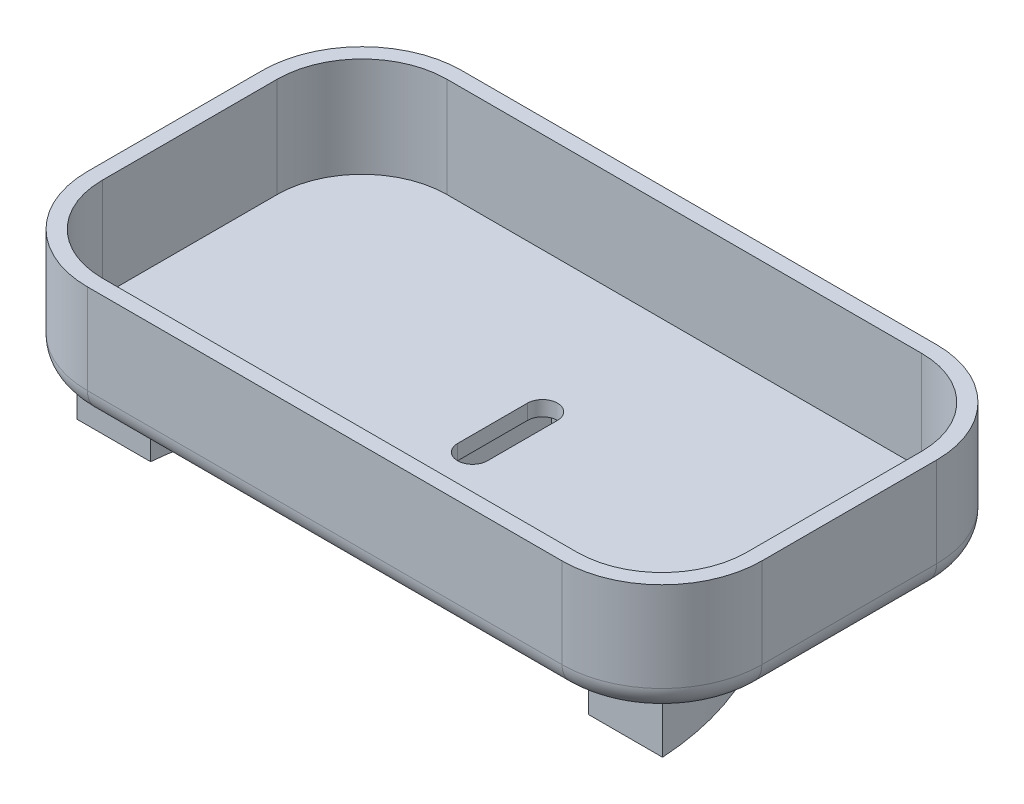
SolidWorks part; units mm, degrees
ref_plane "Front Plane" through (0, 0, 0) normal (0, 0, 1) x (1, 0, 0)
ref_plane "Top Plane" through (0, 0, 0) normal (0, 1, 0) x (1, 0, 0)
ref_plane "Right Plane" through (0, 0, 0) normal (1, 0, 0) x (0, 0, -1)
sketch "Esboço1" plane through (0, 0, 0) normal (0, 1, 0) x (1, 0, 0)
  line L0 (7.7996, 47.1004) -> (7.7996, 20.1004)
  line L1 (7.7996, 20.1004) -> (42.6416, 20.1004)
  line L2 (46.9151, 5.7004) -> (56.2287, 5.7004)
  line L3 (37.717, 41.7004) -> (37.717, 41.7004)
  line L8 (-37.1178, 41.7004) -> (-37.1178, 41.7004)
  line L9 (-55.6295, 5.7004) -> (-46.3158, 5.7004)
  line L10 (-42.0423, 20.1004) -> (-7.2004, 20.1004)
  line L11 (-7.2004, 20.1004) -> (-7.2004, 47.1004)
  line L12 (-7.2004, 47.1004) -> (7.7996, 47.1004)
  line L26 (4.7996, 44.1004) -> (4.7996, 17.1004)
  line L27 (4.7996, 17.1004) -> (40.713, 17.1004)
  line L28 (44.1972, 2.7004) -> (59.4736, 2.7004)
  line L35 (-58.8744, 2.7004) -> (-43.598, 2.7004)
  line L36 (-40.1137, 17.1004) -> (-4.2004, 17.1004)
  line L37 (-4.2004, 17.1004) -> (-4.2004, 44.1004)
  line L38 (-4.2004, 44.1004) -> (4.7996, 44.1004)
  line L39 (-17.7004, 44.7004) -> (-34.5804, 44.7004) construction
  line L40 (-14.7004, 53.9135) -> (-14.7004, 41.7004) construction
  line L41 (-17.7004, 56.15) -> (-17.7004, 44.7004) construction
  line L42 (-14.7004, 41.7004) -> (-37.1178, 41.7004) construction
  line L43 (-34.5804, 44.7004) -> (-34.5804, 47.5955) construction
  line L44 (18.2996, 44.7004) -> (18.2996, 56.15) construction
  line L45 (15.2996, 41.7004) -> (15.2996, 53.9135) construction
  line L46 (37.717, 41.7004) -> (15.2996, 41.7004) construction
  line L47 (35.1796, 44.7004) -> (18.2996, 44.7004) construction
  line L48 (35.1796, 47.5955) -> (35.1796, 44.7004) construction
  arc A0 (46.9151, 5.7004) -> (42.6416, 20.1004) centre (0.2996, -0.2996) ccw
  arc A1 (56.2287, 5.7004) -> (15.2996, 53.9135) centre (0.2996, -0.2996) ccw
  arc A2 (15.2996, 53.9135) -> (-14.7004, 53.9135) centre (0.2996, -0.2996) ccw
  arc A3 (-14.7004, 53.9135) -> (-55.6295, 5.7004) centre (0.2996, -0.2996) ccw
  arc A4 (-42.0423, 20.1004) -> (-46.3158, 5.7004) centre (0.2996, -0.2996) ccw
  arc A5 (-37.1178, 41.7004) -> (-55.6295, 5.7004) centre (0.2996, -0.2996) ccw construction
  arc A6 (-34.5804, 47.5955) -> (-58.8744, 2.7004) centre (0.2996, -0.2996) ccw construction
  arc A7 (56.2287, 5.7004) -> (37.717, 41.7004) centre (0.2996, -0.2996) ccw construction
  arc A8 (59.4736, 2.7004) -> (35.1796, 47.5955) centre (0.2996, -0.2996) ccw construction
  arc A10 (44.1972, 2.7004) -> (40.713, 17.1004) centre (0.2996, -0.2996) ccw
  arc A11 (59.4736, 2.7004) -> (18.2996, 56.15) centre (0.2996, -0.2996) ccw
  arc A12 (18.2996, 56.15) -> (-17.7004, 56.15) centre (0.2996, -0.2996) ccw
  arc A13 (-17.7004, 56.15) -> (-58.8744, 2.7004) centre (0.2996, -0.2996) ccw
  arc A14 (-40.1137, 17.1004) -> (-43.598, 2.7004) centre (0.2996, -0.2996) ccw
  dimension "D1" = 3
extrude "Ressalto-extrusão2" add sketch "Esboço1" along normal blind 10 contours A14 L36 L37 L38 L26 L27 A10 L28 A11 A12 A13 L35 L10 A4 L9 A3 A2 A1 L2 A0 L1 L0 L12 L11 region at (0.2996, 0, -45.4107)
sketch "Esboço3" plane through (0, 10, 0) normal (0, 1, 0) x (1, 0, 0)
  line L0 (-58.8744, 2.7004) -> (59.4736, 2.7004)
  arc A0 (59.4736, 2.7004) -> (-58.8744, 2.7004) centre (0.2996, -0.2996) ccw construction
  arc A1 (59.4736, 2.7004) -> (-58.8744, 2.7004) centre (0.2996, -0.2996) ccw
extrude "Ressalto-extrusão3" add sketch "Esboço3" along normal blind 3
sketch "Esboço4" plane through (0, 10, 0) normal (0, -1, 0) x (1, 0, 0)
  line L0 (0, -24.1004) -> (0, -38.1004) construction
  line L1 (3, -24.1004) -> (3, -38.1004)
  line L2 (-3, -24.1004) -> (-3, -38.1004)
  line L5 (-4.2004, -44.1004) -> (4.7996, -44.1004) construction
  arc A0 (3, -24.1004) -> (-3, -24.1004) centre (0, -24.1004) ccw
  arc A1 (-3, -38.1004) -> (3, -38.1004) centre (0, -38.1004) ccw
  point P3 (0, -31.1004)
  dimension "D1" = 20
  dimension "D3" = 3
  dimension "D2" = 6
extrude "Corte-extrusão1" cut sketch "Esboço4" against normal through all both and the other way through all
sketch "Esboço5" plane through (0, 13, 0) normal (0, 1, 0) x (1, 0, 0)
  line L0 (-58.346, 3.2004) -> (58.9453, 3.2004)
  line L1 (-58.8744, 2.7004) -> (59.4736, 2.7004)
  line L2 (-58.8744, 2.7004) -> (59.4736, 2.7004)
  arc A0 (58.9453, 3.2004) -> (-58.346, 3.2004) centre (0.2996, -0.2996) ccw
  arc A1 (59.4736, 2.7004) -> (-58.8744, 2.7004) centre (0.2996, -0.2996) ccw
  arc A2 (59.4736, 2.7004) -> (-58.8744, 2.7004) centre (0.2996, -0.2996) ccw
  dimension "D1" = 0
  dimension "D2" = 0.5
extrude "Corte-extrusão2" cut sketch "Esboço5" against normal through all
sketch "Esboço7" plane through (0, 13, 0) normal (0, 1, 0) x (1, 0, 0)
  line L0 (-67.2268, -5.7996) -> (-49.8945, -5.7996)
  line L1 (-49.8945, -5.7996) -> (67.826, -5.7996)
  line L4 (-58.346, 3.2004) -> (58.9453, 3.2004)
  line L7 (-58.346, 3.2004) -> (58.9453, 3.2004)
  line L9 (-67.2268, -5.7996) -> (-29.7004, -5.7996) construction
  line L12 (-29.95, 3.6004) -> (29.5415, 3.6004) construction
  line L13 (-37.0345, 12.6004) -> (36.3278, 12.6004) construction
  line L14 (-58.346, 3.2004) -> (-39.045, 3.2004) construction
  arc A1 (67.826, -5.7996) -> (-67.2268, -5.7996) centre (0.2996, -0.2996) ccw
  arc A5 (58.9453, 3.2004) -> (-58.346, 3.2004) centre (0.2996, -0.2996) ccw
  arc A8 (58.9453, 3.2004) -> (-58.346, 3.2004) centre (0.2996, -0.2996) ccw
  arc A12 (-29.95, 3.6004) -> (-29.7004, -5.7996) centre (0.2996, -0.2996) ccw construction
  arc A13 (-49.8945, -5.7996) -> (29.5415, 3.6004) centre (-9.7974, -4.3031) ccw construction
  arc A14 (-37.0345, 12.6004) -> (-39.045, 3.2004) centre (0.2996, -0.2996) ccw construction
  arc A15 (-58.346, 3.2004) -> (36.3278, 12.6004) centre (-9.7974, -4.3031) ccw construction
  dimension "D1" = 0
  dimension "D2" = 9
extrude "Ressalto-extrusão4" add sketch "Esboço7" against normal blind 3
sketch "Esboço13" plane through (0, 13, 0) normal (0, 1, 0) x (1, 0, 0)
  line L0 (-67.2268, -5.7996) -> (-67.2268, 69.2004)
  line L1 (-67.2268, 69.2004) -> (67.826, 69.2004)
  line L2 (67.826, 69.2004) -> (67.826, -5.7996)
  line L3 (67.826, -5.7996) -> (-67.2268, -5.7996)
  line L4 (3, 38.1004) -> (3, 24.1004) construction
  line L5 (-3, 24.1004) -> (-3, 38.1004) construction
  line L6 (3, 38.1004) -> (3, 24.1004)
  line L7 (-3, 24.1004) -> (-3, 38.1004)
  arc A0 (-3, 24.1004) -> (3, 24.1004) centre (0, 24.1004) ccw construction
  arc A1 (3, 38.1004) -> (-3, 38.1004) centre (0, 38.1004) ccw construction
  arc A2 (-3, 24.1004) -> (3, 24.1004) centre (0, 24.1004) ccw
  arc A3 (3, 38.1004) -> (-3, 38.1004) centre (0, 38.1004) ccw
  dimension "D1" = 75
extrude "Ressalto-extrusão10" add sketch "Esboço13" against normal up to surface (3 mm away) up to face at (0.2996, 10, -24.7997)
fillet "Filete1" radius 20 4 edges at (67.826, 11.5, -69.2004) (67.826, 11.5, 5.7996) (-67.2268, 11.5, -69.2004) (-67.2268, 11.5, 5.7996)
sketch "Esboço15" plane through (0, 13, 0) normal (0, 1, 0) x (1, 0, 0)
  line L0 (64.826, 14.2004) -> (64.826, 49.2004)
  line L1 (47.826, 66.2004) -> (-47.2268, 66.2004)
  line L2 (-64.2268, 49.2004) -> (-64.2268, 14.2004)
  line L3 (-47.2268, -2.7996) -> (47.826, -2.7996)
  line L4 (67.826, 14.2004) -> (67.826, 49.2004)
  line L5 (47.826, 69.2004) -> (-47.2268, 69.2004)
  line L6 (-67.2268, 49.2004) -> (-67.2268, 14.2004)
  line L7 (-47.2268, -5.7996) -> (47.826, -5.7996)
  line L8 (67.826, 14.2004) -> (67.826, 49.2004)
  line L9 (47.826, 69.2004) -> (-47.2268, 69.2004)
  line L10 (-67.2268, 49.2004) -> (-67.2268, 14.2004)
  line L11 (-47.2268, -5.7996) -> (47.826, -5.7996)
  arc A0 (64.826, 49.2004) -> (47.826, 66.2004) centre (47.826, 49.2004) ccw
  arc A1 (-47.2268, 66.2004) -> (-64.2268, 49.2004) centre (-47.2268, 49.2004) ccw
  arc A2 (-64.2268, 14.2004) -> (-47.2268, -2.7996) centre (-47.2268, 14.2004) ccw
  arc A3 (47.826, -2.7996) -> (64.826, 14.2004) centre (47.826, 14.2004) ccw
  arc A4 (67.826, 49.2004) -> (47.826, 69.2004) centre (47.826, 49.2004) ccw
  arc A5 (-47.2268, 69.2004) -> (-67.2268, 49.2004) centre (-47.2268, 49.2004) ccw
  arc A6 (-67.2268, 14.2004) -> (-47.2268, -5.7996) centre (-47.2268, 14.2004) ccw
  arc A7 (47.826, -5.7996) -> (67.826, 14.2004) centre (47.826, 14.2004) ccw
  arc A8 (67.826, 49.2004) -> (47.826, 69.2004) centre (47.826, 49.2004) ccw
  arc A9 (-47.2268, 69.2004) -> (-67.2268, 49.2004) centre (-47.2268, 49.2004) ccw
  arc A10 (-67.2268, 14.2004) -> (-47.2268, -5.7996) centre (-47.2268, 14.2004) ccw
  arc A11 (47.826, -5.7996) -> (67.826, 14.2004) centre (47.826, 14.2004) ccw
  dimension "D1" = 0
  dimension "D2" = 3
extrude "Ressalto-extrusão11" add sketch "Esboço15" along normal blind 20
fillet "Filete2" radius 5 7 edges at (-67.2268, 10, -31.7004) (0.2996, 10, 5.7996) (67.826, 10, -31.7004) (61.9682, 10, -63.3425) (0.2996, 10, -69.2004) (-61.3689, 10, -63.3425) (61.9682, 10, -0.0582)
